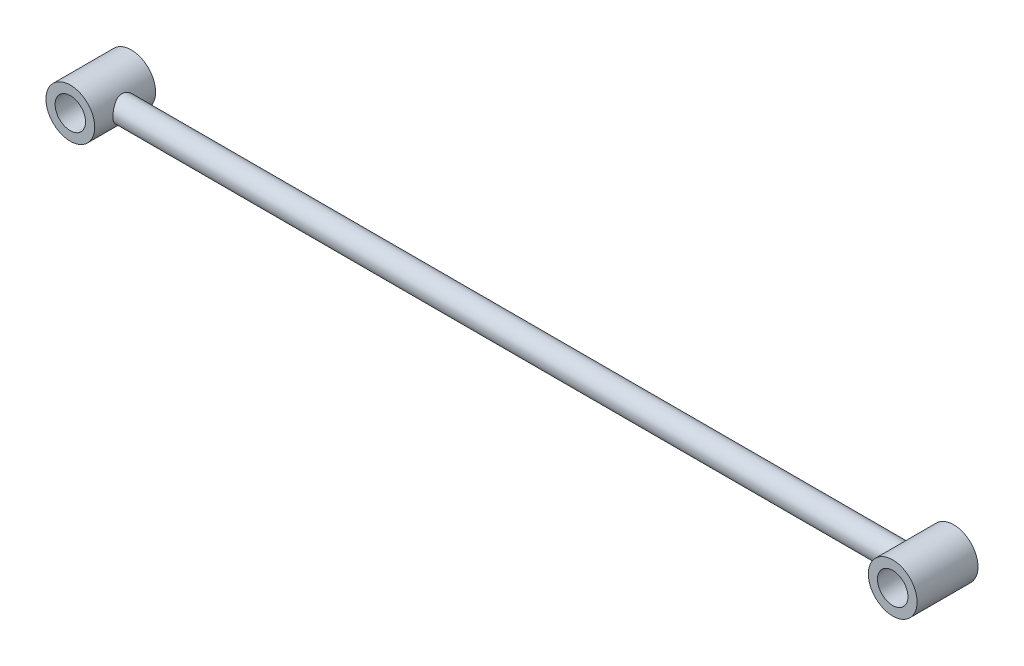
SolidWorks part; units mm, degrees
ref_plane "Front Plane" through (0, 0, 0) normal (0, 0, 1) x (1, 0, 0)
ref_plane "Top Plane" through (0, 0, 0) normal (0, 1, 0) x (1, 0, 0)
ref_plane "Right Plane" through (0, 0, 0) normal (1, 0, 0) x (0, 0, -1)
sketch "Sketch1" plane through (0, 0, 0) normal (0, 0, 1) x (1, 0, 0)
  line L0 (0, 0) -> (67.5, 0) construction
  circle A0 centre (0, 0) radius 1.25
  circle A1 centre (67.5, 0) radius 1.25
  circle A2 centre (0, 0) radius 2
  circle A3 centre (67.5, 0) radius 2
  dimension "D2" = 2.5
  dimension "D3" = 2.5
  dimension "D1" = 67.5
extrude "Boss-Extrude1" add sketch "Sketch1" along normal blind 2.5 and the other way blind 2.5
sketch "Sketch2" plane through (0, 0, 0) normal (0, 0, 1) x (1, 0, 0)
  line L0 (2, 0) -> (65.5, 0) construction
  line L1 (65.5, 0) -> (67.5, 0) construction
  line L2 (67.5, 0) -> (65.7679, 1) construction
  line L3 (65.7679, 1) -> (1.7321, 1)
  line L4 (2.2408, 0) -> (65.5, 0)
  line L5 (1.7321, 1) -> (1.7321, 0)
  line L6 (1.7321, 0) -> (2.2408, 0)
  line L7 (65.7679, 1) -> (65.7679, 0)
  line L8 (65.7679, 0) -> (65.5, 0)
  circle A0 centre (0, 0) radius 2 construction
  circle A1 centre (67.5, 0) radius 2 construction
  arc A2 (65.5, 0) -> (65.7679, 1) centre (67.5, 0) cw
  arc A3 (2, 0) -> (1.7286, 1.0059) centre (0, 0) ccw
  dimension "D1" = 30
revolve "Revolve3" add sketch "Sketch2" angle 360 about L0 region at (33.75, 0.5007, 0)
